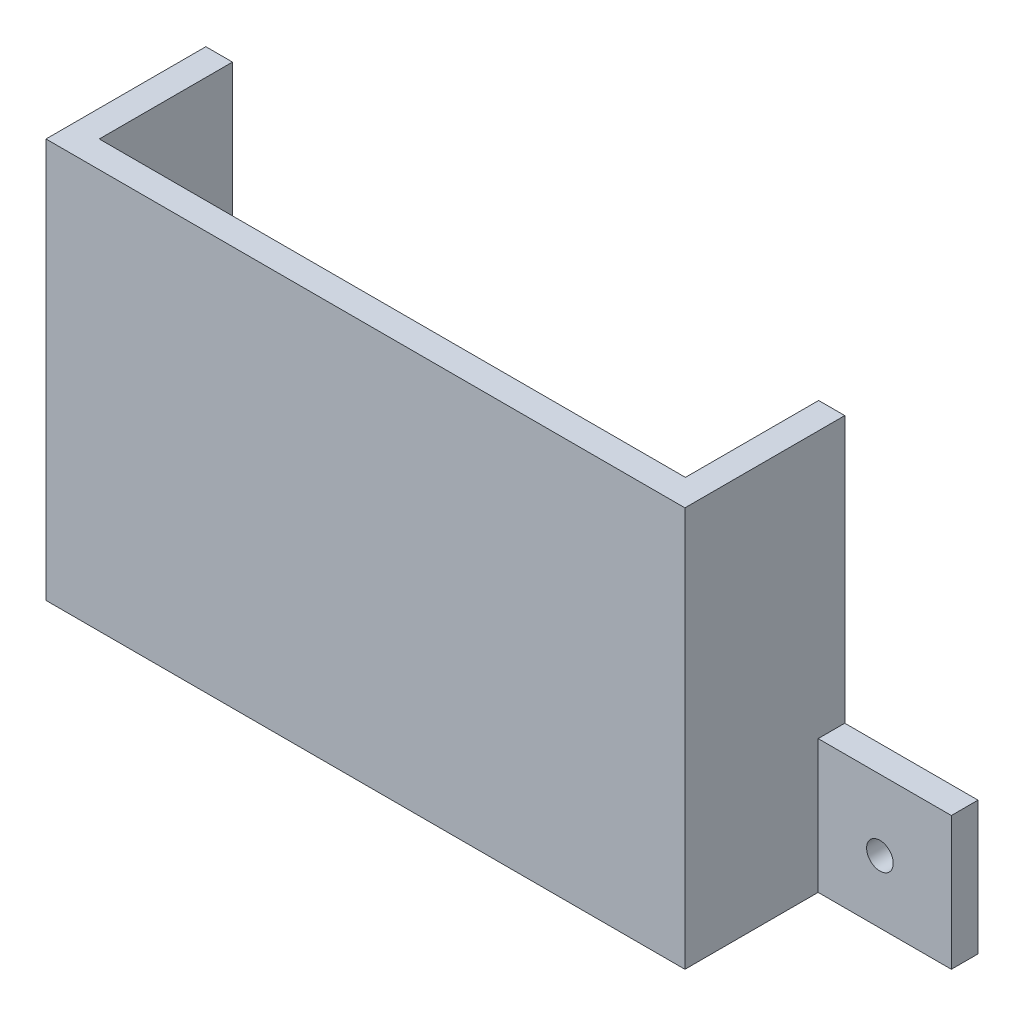
SolidWorks part; units mm, degrees
ref_plane "前视基准面" through (0, 0, 0) normal (0, 0, 1) x (1, 0, 0)
ref_plane "上视基准面" through (0, 0, 0) normal (0, 1, 0) x (1, 0, 0)
ref_plane "右视基准面" through (0, 0, 0) normal (1, 0, 0) x (0, 0, -1)
sketch "草图1" plane through (0, 0, 0) normal (0, 1, 0) x (1, 0, 0)
  line L1 (-38.5263, 0) -> (5.4737, 0)
  line L3 (-38.5263, -2) -> (5.4737, -2)
  line L5 (5.4737, -2) -> (7.4367, -2)
  line L6 (5.4737, 0) -> (5.4737, 10)
  line L7 (5.4737, 10) -> (7.4367, 10)
  line L8 (7.4367, -2) -> (7.4367, 10)
  line L9 (-38.5263, -2) -> (-40.5263, -2)
  line L10 (-38.5263, 0) -> (-38.5263, 10)
  line L11 (-38.5263, 10) -> (-40.5263, 10)
  line L12 (-40.5263, -2) -> (-40.5263, 10)
  dimension "D1" = 2
  dimension "D2" = 44
  dimension "D3" = 10
  dimension "D4" = 2
extrude "凸台-拉伸1" add sketch "草图1" along normal blind 30 contours L1 L6 L7 L8 L5 L3 L9 L12 L11 L10
sketch "草图2" plane through (0, 0, 0) normal (0, 0, 1) x (1, 0, 0)
  line L0 (-40.5263, 0) -> (7.4367, 0) construction
  line L1 (-26.5633, 0) -> (-6.5633, 0)
  line L2 (-26.5633, 0) -> (-26.5633, 2)
  line L3 (-26.5633, 2) -> (-6.5633, 2)
  line L4 (-6.5633, 0) -> (-6.5633, 2)
  line L5 (7.4367, 30) -> (7.4367, 0) construction
  dimension "D1" = 2
  dimension "D2" = 20
  dimension "D3" = 14
extrude "凸台-拉伸2" add sketch "草图2" against normal blind 6 contours L3 L4 L1 L2
sketch "草图3" plane through (0, 0, 0) normal (0, 0, 1) x (1, 0, 0)
  line L0 (-40.5263, 30) -> (-40.5263, 0) construction
  line L1 (-40.5263, 10) -> (-50.5263, 10)
  line L2 (-40.5263, 10) -> (-40.5263, 0)
  line L3 (-40.5263, 0) -> (-50.5263, 0)
  line L4 (-50.5263, 10) -> (-50.5263, 0)
  line L5 (-40.5263, 0) -> (7.4367, 0) construction
  line L6 (7.4367, 30) -> (7.4367, 0) construction
  line L7 (7.4367, 10) -> (17.4367, 10)
  line L8 (7.4367, 10) -> (7.4367, 0)
  line L9 (7.4367, 0) -> (17.4367, 0)
  line L10 (17.4367, 10) -> (17.4367, 0)
  dimension "D1" = 10
  dimension "D2" = 10
  dimension "D3" = 0
  dimension "D4" = 10
  dimension "D5" = 10
extrude "凸台-拉伸5" add sketch "草图3" against normal blind 10
extrude "切除-拉伸1" cut sketch "草图3<2>" against normal blind 8
sketch "草图3<2>" plane through (0, 0, 0) normal (0, 0, 1) x (1, 0, 0) same geometry as "草图3"
sketch "草图4" plane through (0, 0, 0) normal (0, 0, 1) x (1, 0, 0)
  circle A0 centre (-45.8677, 4.7069) radius 1
  circle A1 centre (12.0751, 4.7069) radius 1
  dimension "D1" = 2
  dimension "D2" = 2
extrude "切除-拉伸2" cut sketch "草图4" against normal blind 15
